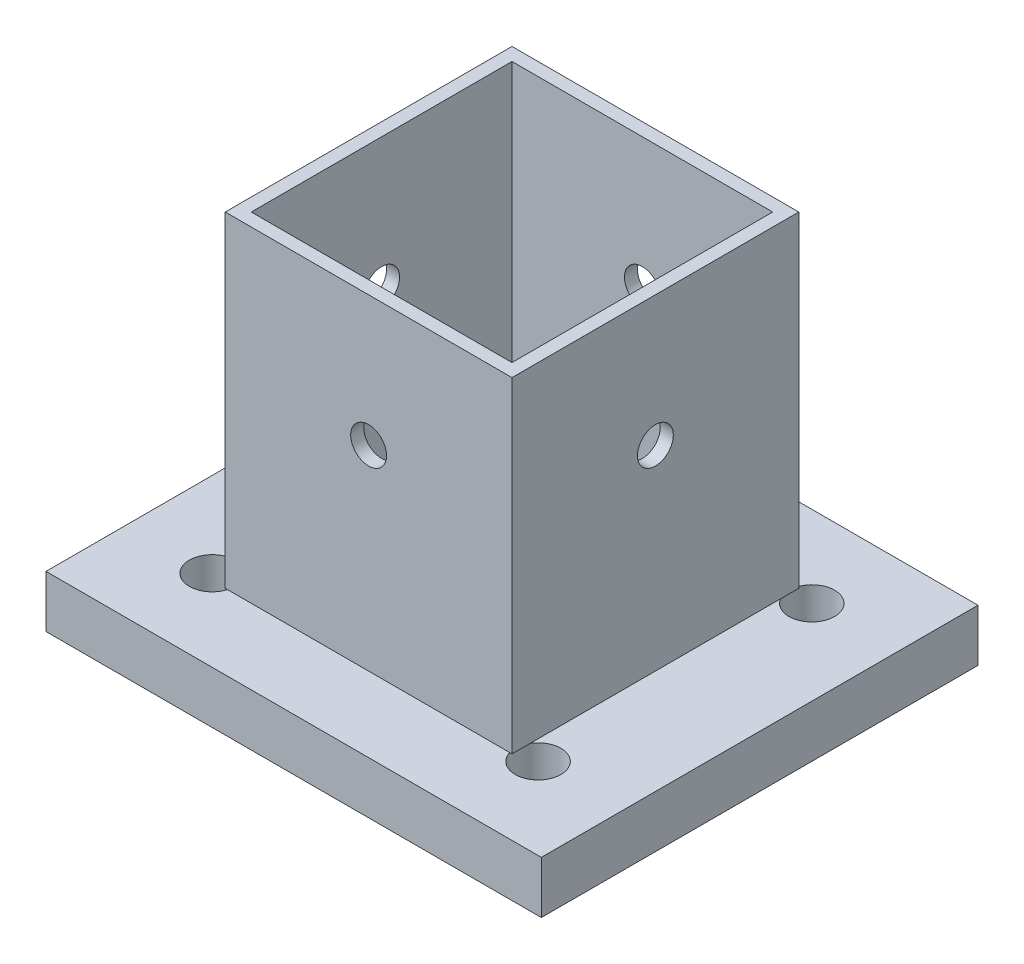
SolidWorks part; units mm, degrees
material "ПВХ пластифицированный"
ref_plane "Спереди" through (0, 0, 0) normal (0, 0, 1) x (1, 0, 0)
ref_plane "Сверху" through (0, 0, 0) normal (0, 1, 0) x (1, 0, 0)
ref_plane "Справа" through (0, 0, 0) normal (1, 0, 0) x (0, 0, -1)
ref_axis "ОсьX" through (-88.99, 0, 0) along (1, 0, 0)
ref_axis "ОсьZ" through (0, 55, 0) along (0, -1, 0)
ref_axis "ОсьY" through (0, 0, -88.99) along (0, 0, 1)
sketch "Эскиз1" plane through (0, 0, 0) normal (0, 1, 0) x (1, 0, 0)
  line L0 (-13.3703, 0) -> (0, 0) construction
  line L1 (38, 33.5) -> (-38, 33.5)
  line L2 (38, 33.5) -> (38, -33.5)
  line L3 (38, -33.5) -> (-38, -33.5)
  line L4 (-38, 33.5) -> (-38, -33.5)
  line L5 (38, 33.5) -> (-38, -33.5) construction
  line L6 (38, -33.5) -> (-38, 33.5) construction
  line L7 (0, 0) -> (0, 14.132) construction
  circle A0 centre (-25, 21) radius 3.5
  circle A1 centre (25, 21) radius 3.5
  circle A2 centre (25, -21) radius 3.5
  circle A3 centre (-25, -21) radius 3.5
  point P0 (0, 0)
  dimension "D3" = 50
  dimension "D4" = 42
  dimension "D5" = 7
  dimension "D1" = 67
  dimension "D2" = 76
extrude "Бобышка-Вытянуть1" add sketch "Эскиз1" along normal blind 8
sketch "Эскиз2" plane through (0, 8, 0) normal (0, 1, 0) x (1, 0, 0)
  line L1 (20, 20) -> (-20, 20)
  line L2 (20, 20) -> (20, -20)
  line L3 (20, -20) -> (-20, -20)
  line L4 (-20, 20) -> (-20, -20)
  line L5 (20, 20) -> (-20, -20) construction
  line L6 (20, -20) -> (-20, 20) construction
  point P0 (0, 0)
  dimension "D1" = 40
  dimension "D2" = 40
extrude "Вытянуть-Тонкостенный1" add sketch "Эскиз2" along normal blind 50 thin thin type one direction wall 2
sketch "Эскиз3" plane through (0, 0, 22) normal (0, 0, 1) x (1, 0, 0)
  line L0 (-22, 58) -> (22, 58) construction
  circle A0 centre (0, 38) radius 2.75
  dimension "D1" = 5.5
  dimension "D2" = 20
extrude "Вырез-Вытянуть1" cut sketch "Эскиз3" against normal up to next
pattern_circular "Круговой массив1" count 4 over 360 about axis through (0, 55, 0) along (0, -1, 0) of "Вырез-Вытянуть1"
